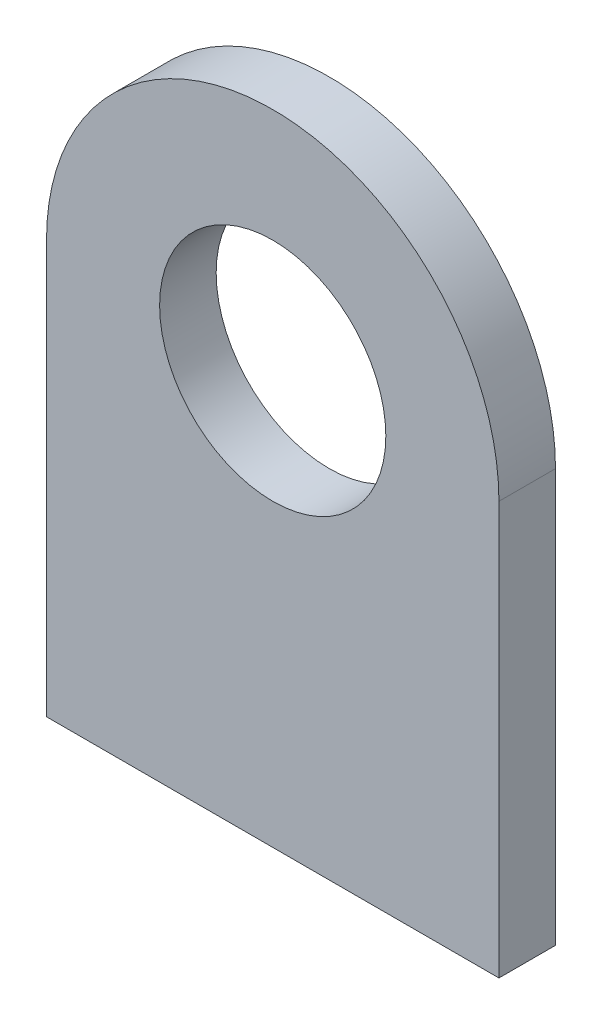
SolidWorks part; units mm, degrees
ref_plane "Front Plane" through (0, 0, 0) normal (0, 0, 1) x (1, 0, 0)
ref_plane "Top Plane" through (0, 0, 0) normal (0, 1, 0) x (1, 0, 0)
ref_plane "Right Plane" through (0, 0, 0) normal (1, 0, 0) x (0, 0, -1)
sketch "Sketch1" plane through (0, 0, 0) normal (0, 0, 1) x (1, 0, 0)
  line L0 (7.9877, -2.8207) -> (20.6877, -2.8207) construction
  line L1 (20.6877, -2.8207) -> (20.6877, 20.3568) construction
  line L2 (20.6877, 20.3568) -> (20.6877, 33.0568) construction
  line L3 (20.6877, 20.3568) -> (14.3377, 20.3568) construction
  line L5 (7.9877, 20.3568) -> (7.9877, -2.8207)
  line L8 (33.3877, 20.3568) -> (33.3877, -2.8207)
  line L9 (7.9877, -2.8207) -> (33.3877, -2.8207)
  line L14 (20.6877, 60.7428) -> (20.6877, 63.9178) construction
  circle A0 centre (20.6877, 20.3568) radius 6.35
  arc A9 (33.3877, 20.3568) -> (7.9877, 20.3568) centre (20.6877, 20.3568) ccw
  dimension "D2" = 12.7
  dimension "D1" = 23.1775
  dimension "D3" = 43.561
extrude "Boss-Extrude1" add sketch "Sketch1" along normal blind 3.175
